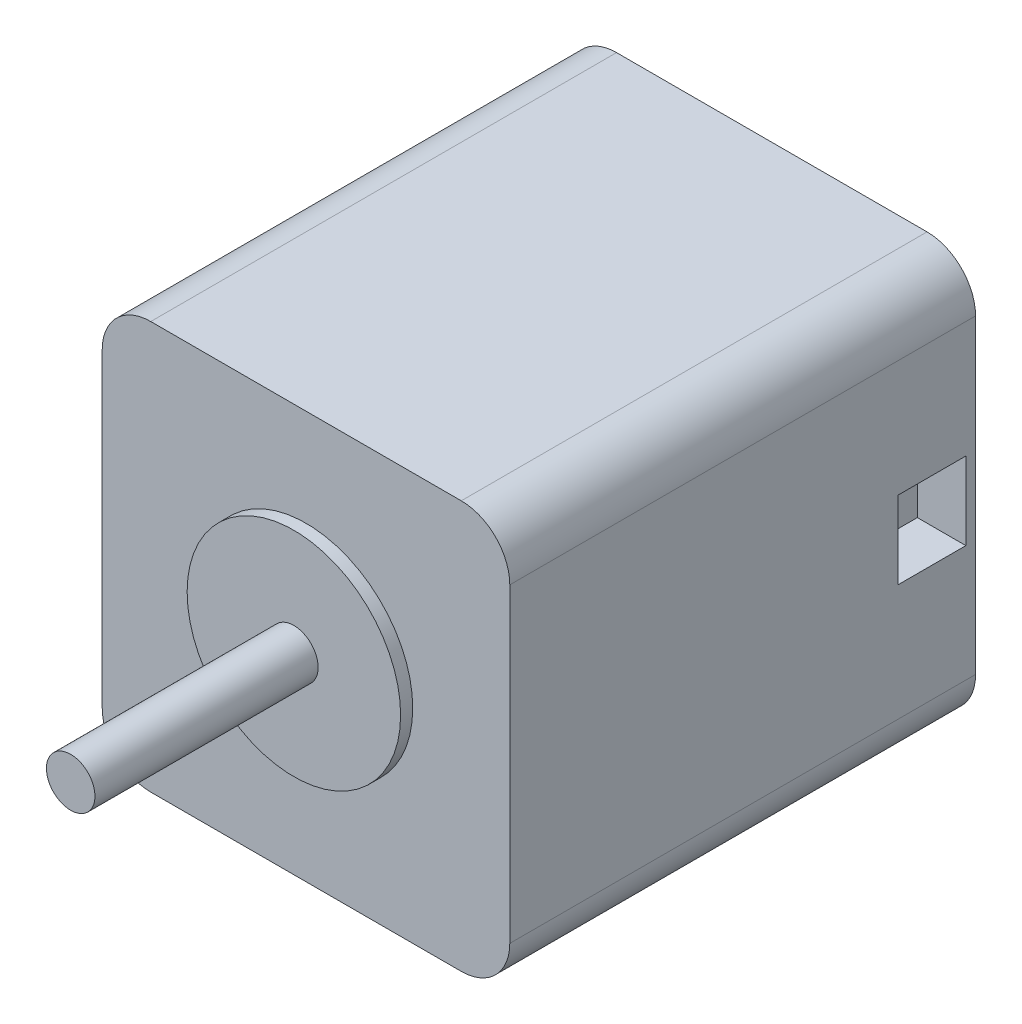
SolidWorks part; units mm, degrees
ref_plane "Front Plane" through (0, 0, 0) normal (1, 0, 0) x (0, 1, 0)
ref_plane "Top Plane" through (0, 0, 0) normal (0, 0, 1) x (0, 1, 0)
ref_plane "Right Plane" through (0, 0, 0) normal (0, 1, 0) x (-1, 0, 0)
sketch "Sketch1" plane through (0, 0, 0) normal (0, 0, 1) x (0, 1, 0)
  line L1 (-21, -21) -> (21, -21)
  line L2 (-21, -21) -> (-21, 21)
  line L3 (-21, 21) -> (21, 21)
  line L4 (21, -21) -> (21, 21)
  line L5 (-21, -21) -> (21, 21) construction
  line L6 (-21, 21) -> (21, -21) construction
  point P0 (0, 0)
  dimension "D1" = 42
  dimension "D2" = 42
extrude "Boss-Extrude1" add sketch "Sketch1" along normal mid plane 48
sketch "Sketch2" plane through (0, 0, 0) normal (1, 0, 0) x (0, 1, 0)
  line L0 (-21, -24) -> (21, -24) construction
  line L1 (-4, -23) -> (4, -23)
  line L2 (-4, -23) -> (-4, -16)
  line L3 (-4, -16) -> (4, -16)
  line L4 (4, -23) -> (4, -16)
  line L5 (-4, -23) -> (4, -16) construction
  line L6 (-4, -16) -> (4, -23) construction
  point P0 (0, -19.5)
  point P7 (0, 0)
  dimension "D1" = 8
  dimension "D2" = 7
  dimension "D3" = 1
extrude "Cut-Extrude1" cut sketch "Sketch2" against normal blind 5 from surface starting at face at (21, 0, 0)
sketch "Sketch3" plane through (0, 0, 0) normal (0, 0, 1) x (0, 1, 0)
  circle A0 centre (0, 0) radius 2.5
  circle A1 centre (0, 0) radius 11
  dimension "D1" = 5
  dimension "D2" = 22
extrude "Boss-Extrude2" add sketch "Sketch3" along normal mid plane 2.5 from surface contours A1 A0 region at (0, -10.6889, 0) starting at face at (0, 0, 24)
extrude "Boss-Extrude3" add sketch "Sketch3<3>" along normal blind 23 from surface separate body contours A0 starting at face at (-2.5, 0, 25.25)
sketch "Sketch3<3>" plane through (0, 0, 0) normal (0, 0, 1) x (0, 1, 0) same geometry as "Sketch3"
fillet "Fillet1" radius 5 4 edges at (21, -21, 0) (-21, 21, 0) (-21, -21, 0) (21, 21, 0)
